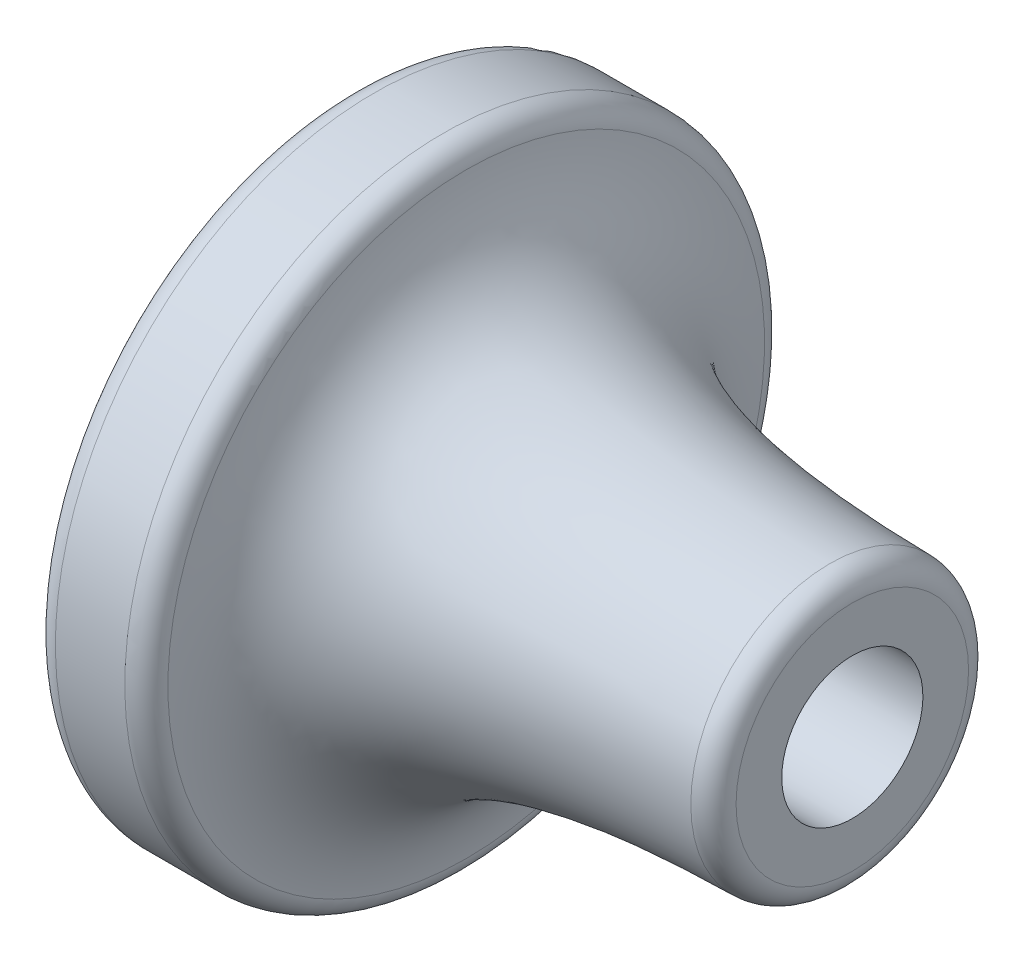
SolidWorks part; units mm, degrees
ref_plane "Front Plane" through (0, 0, 0) normal (0, 0, 1) x (1, 0, 0)
ref_plane "Top Plane" through (0, 0, 0) normal (0, 1, 0) x (1, 0, 0)
ref_plane "Right Plane" through (0, 0, 0) normal (1, 0, 0) x (0, 0, -1)
sketch "Sketch1" plane through (0, 0, 0) normal (0, 0, 1) x (1, 0, 0)
  line L0 (0, 0) -> (0, 3.1)
  line L1 (0, 3.1) -> (14, 3.1)
  line L2 (14, 3.1) -> (14, 6.1)
  line L3 (0, 0) -> (-8, 0)
  line L4 (-8, 0) -> (-8, 14)
  line L5 (-8, 14) -> (-3, 14)
  line L6 (50, 3) -> (0, 3) construction
  line L7 (-3, 14) -> (-3, 0) construction
  line L8 (14, 6.1) -> (-8, 6.1) construction
  spline S0 degree 3 poles (-3, 14) (-3, 8.8674) (0.9614, 6.1) (14, 6.1) knots 0 0 0 0 1 1 1 1
  dimension "D1" = 14
  dimension "D2" = 0.1
  dimension "D3" = 22
  dimension "D4" = 8
  dimension "D5" = 3
  dimension "D6" = 5
revolve "Revolve1" add sketch "Sketch1" angle 360 about L3
fillet "Fillet1" radius 1 3 edges at (-8, 14, 0) (-3, 14, 0) (14, 6.1, 0)
